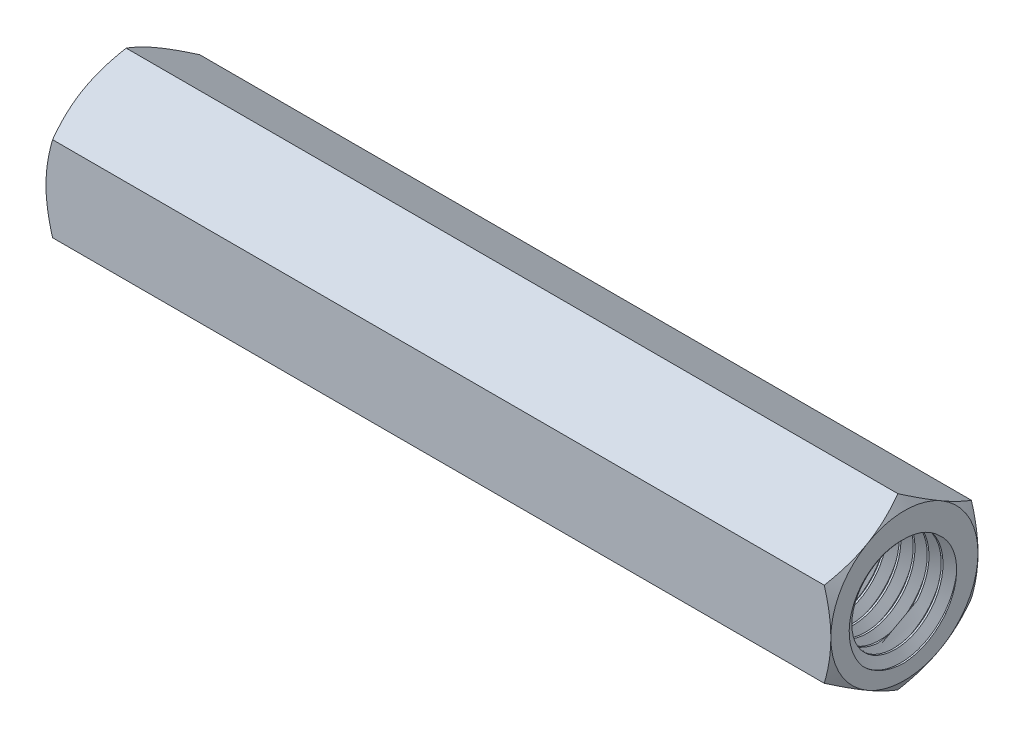
SolidWorks part; units mm, degrees
note: '?' marks a value the reader was unsure of.
ref_plane "Front Plane" through (0, 0, 0) normal (0, 0, 1) x (1, 0, 0)
ref_plane "Top Plane" through (0, 0, 0) normal (0, 1, 0) x (1, 0, 0)
ref_plane "Right Plane" through (0, 0, 0) normal (1, 0, 0) x (0, 0, -1)
sketch "Sketch1" plane through (0, 0, 0) normal (0, 0, 1) x (1, 0, 0)
  line L0 (-25.4, 0) -> (25.4, 0) construction
  line L1 (-25.4, 3.175) -> (-25.4, -3.175) construction
  line L2 (25.4, 3.175) -> (25.4, -3.175) construction
  line L3 (0, 4.7625) -> (0, -4.7625) construction
  line L4 (6.35, 3.175) -> (6.35, -3.175) construction
  line L5 (-6.35, 3.175) -> (-6.35, -3.175) construction
  line L6 (-25.4, 3.175) -> (-6.35, 3.175) construction
  line L7 (-25.4, -3.175) -> (-6.35, -3.175) construction
  line L8 (6.35, -3.175) -> (25.4, -3.175) construction
  line L9 (6.35, 3.175) -> (25.4, 3.175) construction
  point P7 (-6.35, 0)
  point P8 (6.35, 0)
  point P17 (18.1429, -3.175)
  dimension "Length" = 50.8
  dimension "D1" = 19.05
  dimension "Thread Size" = 6.35
  dimension "Rod OD" = 9.525
  dimension "Thread Length" = 19.05
  dimension "D2" = 12.7
  dimension "D5" = 7.2571
sketch "Sketch2" plane through (0, 0, 0) normal (1, 0, 0) x (0, 0, -1)
  line L1 (4.7625, 2.7496) -> (0, 5.4993)
  line L2 (0, 5.4993) -> (-4.7625, 2.7496)
  line L3 (-4.7625, 2.7496) -> (-4.7625, -2.7496)
  line L4 (-4.7625, -2.7496) -> (0, -5.4993)
  line L5 (0, -5.4993) -> (4.7625, -2.7496)
  line L6 (4.7625, -2.7496) -> (4.7625, 2.7496)
  circle A1 centre (0, 0) radius 4.7625 construction
  point P12 (0, 4.7625)
extrude "Boss-Extrude1" add sketch "Sketch2" against normal up to vertex (25.4 mm away) and the other way up to vertex (25.4 mm away) up to point (-25.4, 0, 0) other way up to point (25.4, 0, 0)
sketch "Sketch4" plane through (-25.4, 0, 0) normal (-1, 0, 0) x (0, 0, 1)
  circle A0 centre (0, 0) radius 3.175
extrude "Cut-Extrude1" cut sketch "Sketch4" against normal up to vertex (19.05 mm away) up to point (-6.35, 0, 0)
sketch "Sketch7" plane through (-6.35, 0, 0) normal (-1, 0, 0) x (0, 0, 1)
  circle A1 centre (0, 0) radius 3.175
  circle A2 centre (0, 0) radius 3.175
  dimension "D1" = 0
extrude "Cut-Extrude2" cut sketch "Sketch7" against normal through all draft 59
sketch "Sketch5" plane through (-25.4, 0, 0) normal (-1, 0, 0) x (0, 0, 1)
  line L0 (0, 5.4993) -> (4.7625, 2.7496) construction
  circle A0 centre (0, 0) radius 4.7625
extrude "Cut-Extrude-Thin2" cut sketch "Sketch5" against normal through all draft 60 thin
mirror "Mirror1" about plane through (0, 0, 0) normal (1, 0, 0) of "Cut-Extrude1", "Cut-Extrude-Thin2", "Cut-Extrude2"
sketch "Sketch3" plane through (-25.4, 0, 0) normal (1, 0, 0) x (0, 0, -1)
  circle A0 centre (0, 0) radius 3.175 construction
  circle A1 centre (0, 0) radius 3.175
curve "Helix/Spiral1" pitch 0.9071 height 19.05 turns 21 parameters "pitch"=0.9071
sketch "Sketch6" plane through (0, 0, 0) normal (0, 0, 1) x (1, 0, 0)
  line L0 (-26.2504, 3.0768) -> (-25.3433, 3.0768) construction
  line L1 (-25.3433, 3.0768) -> (-25.7969, 3.8624) construction
  line L2 (-25.7969, 3.8624) -> (-26.2504, 3.0768) construction
  line L3 (-26.1937, 3.175) -> (-25.4, 3.175) construction
  line L4 (-25.7969, 3.0768) -> (-25.7969, 3.175) construction
  line L5 (-26.2221, 3.1259) -> (-25.3717, 3.1259) construction
  line L6 (-25.8536, 3.7642) -> (-25.7402, 3.7642) construction
  line L7 (-25.7969, 3.7642) -> (-25.7969, 3.8624) construction
  line L8 (-25.8536, 3.7642) -> (-25.7402, 3.7642) construction
  line L10 (-25.8536, 3.7642) -> (-26.2221, 3.1259)
  line L11 (-26.2221, 3.1259) -> (-25.3717, 3.1259)
  line L12 (-25.3717, 3.1259) -> (-25.7402, 3.7642)
  line L13 (-25.8536, 3.7642) -> (-25.7402, 3.7642)
  point P10 (-25.7969, 3.1259)
  dimension "D1" = 0.9071
  dimension "D2" = 0.1134
sweep "Cut-Sweep1" cut profiles "Sketch6" path "Helix/Spiral1"
mirror "Mirror2" about plane through (0, 0, 0) normal (1, 0, 0) of "Cut-Sweep1"
ref_axis "Center Axis 1" through (-84.6505, 0, 0) along (1, 0, 0)?
ref_plane "Contact Plane 1" through (-25.4, 0, 0) normal (-1, 0, 0) x (0, 0, 1)
ref_plane "Contact Plane 2" through (25.4, 0, 0) normal (1, 0, 0) x (0, 0, -1)
equation "\"D1@Sketch1\" = \"Thread Length@Sketch1\""
equation "\"D3@Helix/Spiral1\"=\"Thread Length@Sketch1\""
equation "\"D5@Sketch1\" = \"pitch@Helix/Spiral1\"*8"
equation "\"D1@Sketch6\"=\"pitch@Helix/Spiral1\""
equation "\"D2@Sketch6\"=\"D1@Sketch6\"/ 1/8"
